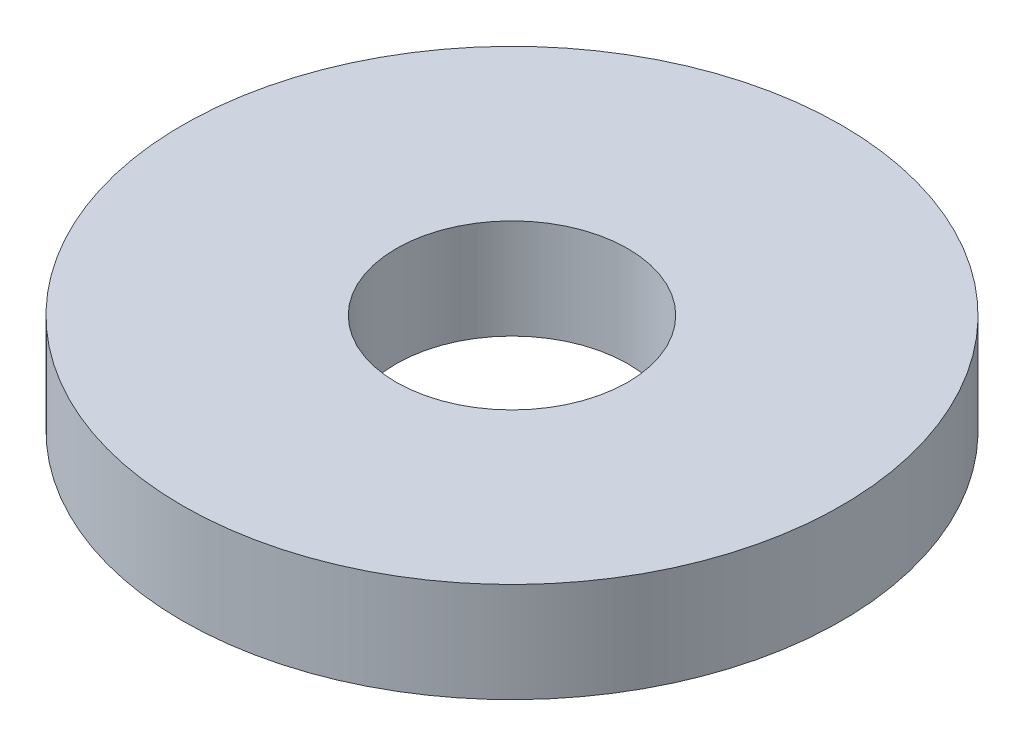
SolidWorks part; units mm, degrees
ref_plane "Front Plane" through (0, 0, 0) normal (0, 0, 1) x (1, 0, 0)
ref_plane "Top Plane" through (0, 0, 0) normal (0, 1, 0) x (1, 0, 0)
ref_plane "Right Plane" through (0, 0, 0) normal (1, 0, 0) x (0, 0, -1)
sketch "Sketch1" plane through (0, 0, 0) normal (0, 1, 0) x (1, 0, 0)
  circle A0 centre (0, 0) radius 92.5
  dimension "FLANGE_OD" = 185
extrude "Boss-Extrude1" add sketch "Sketch1" along normal blind 28
sketch "Sketch2" plane through (0, 0, 0) normal (0, 1, 0) x (1, 0, 0)
  circle A0 centre (0, 0) radius 32.5
  dimension "BORE_D" = 65
extrude "Cut-Extrude1" cut sketch "Sketch2" along normal through all
sketch "Sketch3" plane through (0, 28, 0) normal (0, 1, 0) x (1, 0, 0)
  circle A0 centre (0, 0) radius 23.7591 construction
  circle A1 centre (-23.7591, 0) radius 5.312
  dimension "BOLT_D" = 10.624
  dimension "BOLT_PCD" = 47.5183
extrude "Cut-Extrude2" cut sketch "Sketch3" against normal blind 22.0342 rebuild error yes
pattern_circular "CirPattern1" count 4 over 360 rebuild error yes
